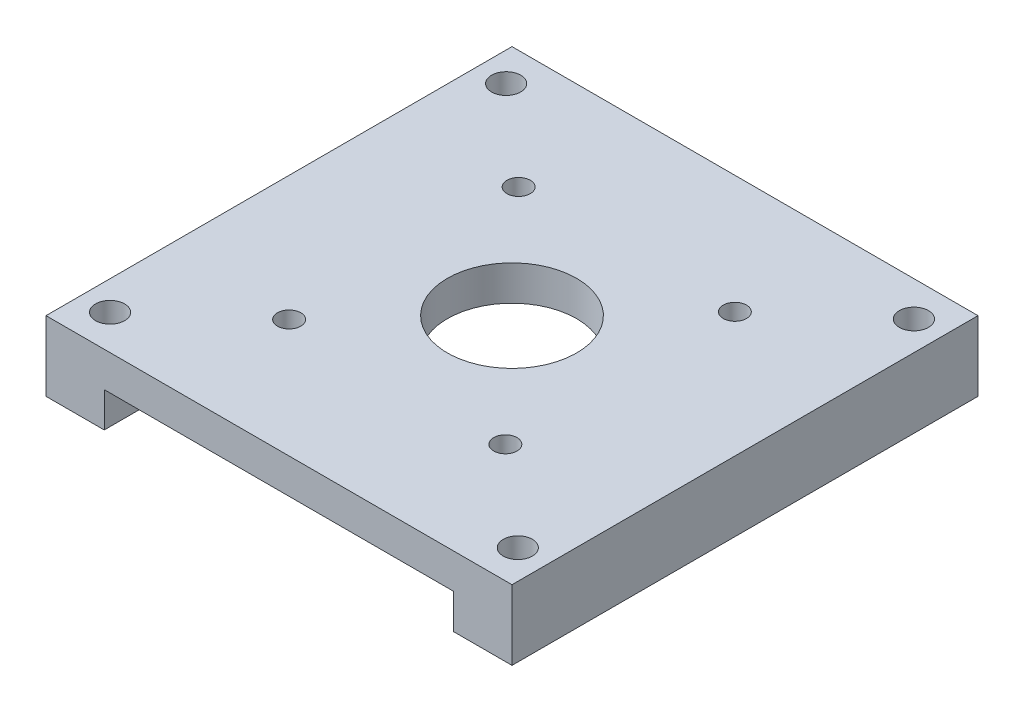
SolidWorks part; units mm, degrees
material "AISI 1020"
ref_plane "Front Plane" through (0, 0, 0) normal (0, 0, 1) x (1, 0, 0)
ref_plane "Top Plane" through (0, 0, 0) normal (0, 1, 0) x (1, 0, 0)
ref_plane "Right Plane" through (0, 0, 0) normal (1, 0, 0) x (0, 0, -1)
sketch "Sketch1" plane through (0, 0, 0) normal (0, 1, 0) x (1, 0, 0)
  line L0 (0, 0) -> (50.8, 50.8)
  line L1 (0, 0) -> (101.6, 0)
  line L2 (0, 0) -> (0, 101.6)
  line L3 (0, 101.6) -> (101.6, 101.6)
  line L4 (101.6, 0) -> (101.6, 101.6)
  line L6 (0, 101.6) -> (12.7, 101.6)
  line L7 (27.2288, 78.867) -> (27.2288, 75.819)
  line L16 (27.2288, 22.733) -> (27.2288, 25.781)
  line L17 (0, 101.6) -> (0, 0)
  line L18 (0, 0) -> (12.7, 0)
  line L19 (12.7, 101.6) -> (12.7, 0)
  line L20 (101.6, 101.6) -> (88.9, 101.6)
  line L21 (101.6, 101.6) -> (101.6, 0)
  line L22 (101.6, 0) -> (88.9, 0)
  line L23 (88.9, 101.6) -> (88.9, 0)
  circle A1 centre (27.2288, 75.819) radius 2.54
  circle A2 centre (74.3712, 75.819) radius 2.54
  circle A3 centre (27.2288, 25.781) radius 2.54
  circle A4 centre (74.3712, 25.781) radius 2.54
  circle A5 centre (50.8, 50.8) radius 14.097
  dimension "D10" = 5.08
  dimension "D12" = 5.08
  dimension "D13" = 5.08
  dimension "D14" = 5.08
  dimension "D3" = 28.194
  dimension "D1" = 101.6
  dimension "D2" = 101.6
  dimension "D4" = 12.7
  dimension "D5" = 12.7
  dimension "D9" = 3.048
  dimension "D11" = 3.048
extrude "Boss-Extrude1" add sketch "Sketch1" along normal blind 7.62 contours L19 L3 L2 L0 | L19 L0 L1 | A5 A3 L19 L1 L23 L3 A4 A2 A1 | L3 L23 L1 L4 region at (6.2089, 0, -53.9044) region at (8.4667, 0, -4.2333) region at (13.97, 0, -57.15) region at (95.25, 0, -50.8)
extrude "Boss-Extrude2" add sketch "Sketch1<3>" against normal blind 7.62 contours L19 L3 L2 L0 | L19 L0 L1 | L3 L23 L1 L4 region at (6.2089, 0, -53.9044) region at (8.4667, 0, -4.2333) region at (95.25, 0, -50.8)
sketch "Sketch1<3>" plane through (0, 0, 0) normal (0, 1, 0) x (1, 0, 0) same geometry as "Sketch1"
sketch "Sketch3" plane through (0, -7.62, 0) normal (0, -1, 0) x (1, 0, 0)
  line L0 (27.2288, -25.781) -> (6.35, -25.781)
  line L1 (12.7, -101.6) -> (12.7, 0) construction
  line L2 (6.35, 0) -> (6.35, -7.62)
  line L3 (74.3712, -25.781) -> (95.25, -25.781)
  line L4 (0, 0) -> (12.7, 0) construction
  line L5 (88.9, -101.6) -> (88.9, 0) construction
  line L7 (27.2288, -75.819) -> (4.977, -75.819)
  line L8 (6.35, -101.6) -> (6.35, -93.98)
  line L10 (0, -101.6) -> (12.7, -101.6) construction
  circle A0 centre (6.35, -7.62) radius 3.175
  circle A1 centre (95.25, -7.62) radius 3.175
  circle A2 centre (6.35, -93.98) radius 3.175
  circle A3 centre (95.25, -93.98) radius 3.175
  dimension "D3" = 6.35
  dimension "D6" = 6.35
  dimension "D7" = 6.35
  dimension "D8" = 6.35
  dimension "D1" = 6.35
  dimension "D2" = 7.62
  dimension "D4" = 6.35
  dimension "D5" = 7.62
extrude "Cut-Extrude1" cut sketch "Sketch3" against normal blind 25.4 contours A3 | A1 | A0 | A2 region at (4.1684, -7.62, -9.8016) region at (95.25, -7.62, -7.62) region at (8.5316, -7.62, -96.1616) region at (95.25, -7.62, -93.98)
